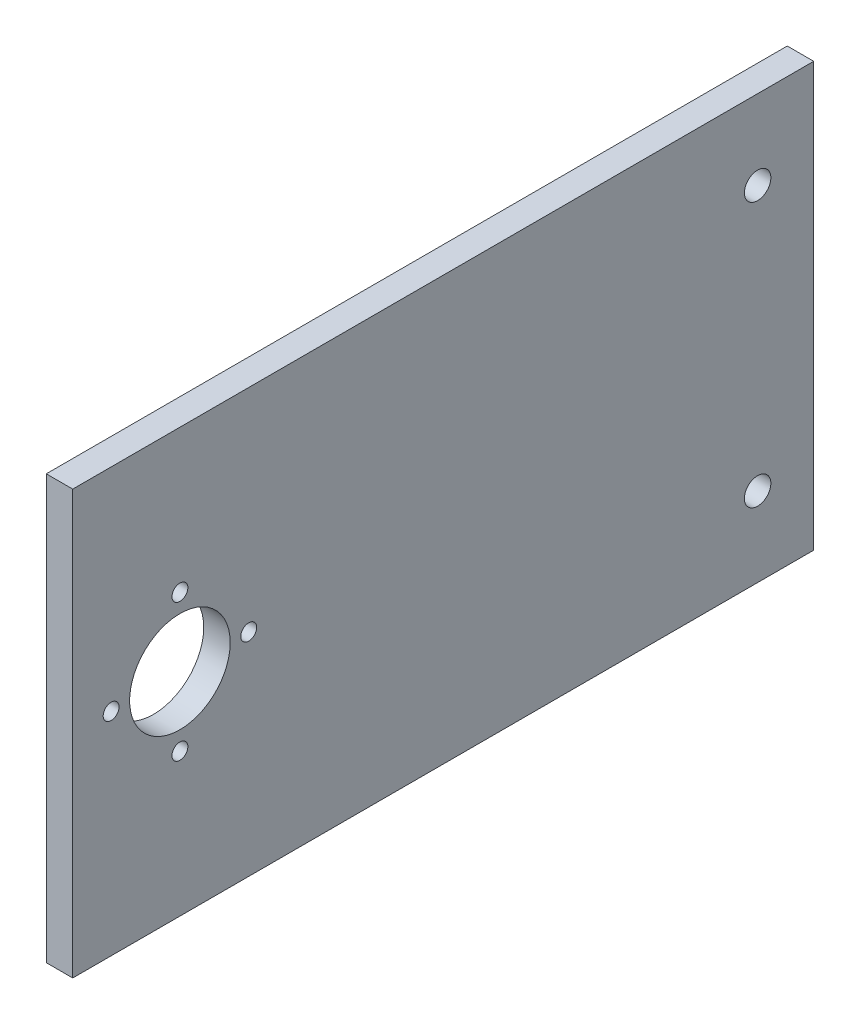
SolidWorks part; units mm, degrees
ref_plane "Front Plane" through (0, 0, 0) normal (1, 0, 0) x (0, 1, 0)
ref_plane "Top Plane" through (0, 0, 0) normal (0, 0, 1) x (0, 1, 0)
ref_plane "Right Plane" through (0, 0, 0) normal (0, 1, 0) x (-1, 0, 0)
sketch "Sketch1" plane through (0, 0, 0) normal (1, 0, 0) x (0, 1, 0)
  line L0 (0, 70) -> (0, -70) construction
  line L1 (-40, -70) -> (40, -70)
  line L2 (-40, -70) -> (-40, 70)
  line L3 (-40, 70) -> (40, 70)
  line L4 (40, -70) -> (40, 70)
  line L5 (-40, -70) -> (40, 70) construction
  line L6 (-40, 70) -> (40, -70) construction
  line L7 (-40, 49.75) -> (40, 49.75) construction
  line L9 (-25, -59.4) -> (25, -59.4) construction
  line L10 (-25, -59.4) -> (-25, 59.4) construction
  line L11 (-25, 59.4) -> (25, 59.4) construction
  line L12 (25, -59.4) -> (25, 59.4) construction
  line L13 (-25, -59.4) -> (25, 59.4) construction
  line L14 (-25, 59.4) -> (25, -59.4) construction
  circle A1 centre (0, 62.75) radius 1.5
  circle A2 centre (0, 36.75) radius 1.5
  circle A3 centre (-13, 49.75) radius 1.5
  circle A4 centre (13, 49.75) radius 1.5
  circle A5 centre (0, 49.75) radius 9.5
  circle A6 centre (-25, -59.4) radius 2.5
  circle A7 centre (25, -59.4) radius 2.5
  point P0 (0, 0)
  point P20 (0, 0)
  dimension "D5" = 3
  dimension "D6" = 3
  dimension "D7" = 13
  dimension "D8" = 19
  dimension "D11" = 5
  dimension "D12" = 5
  dimension "D1" = 80
  dimension "D2" = 140
  dimension "D3" = 119.75
  dimension "D4" = 13
  dimension "D9" = 10.6
  dimension "D10" = 50
extrude "Boss-Extrude1" add sketch "Sketch1" along normal blind 5
